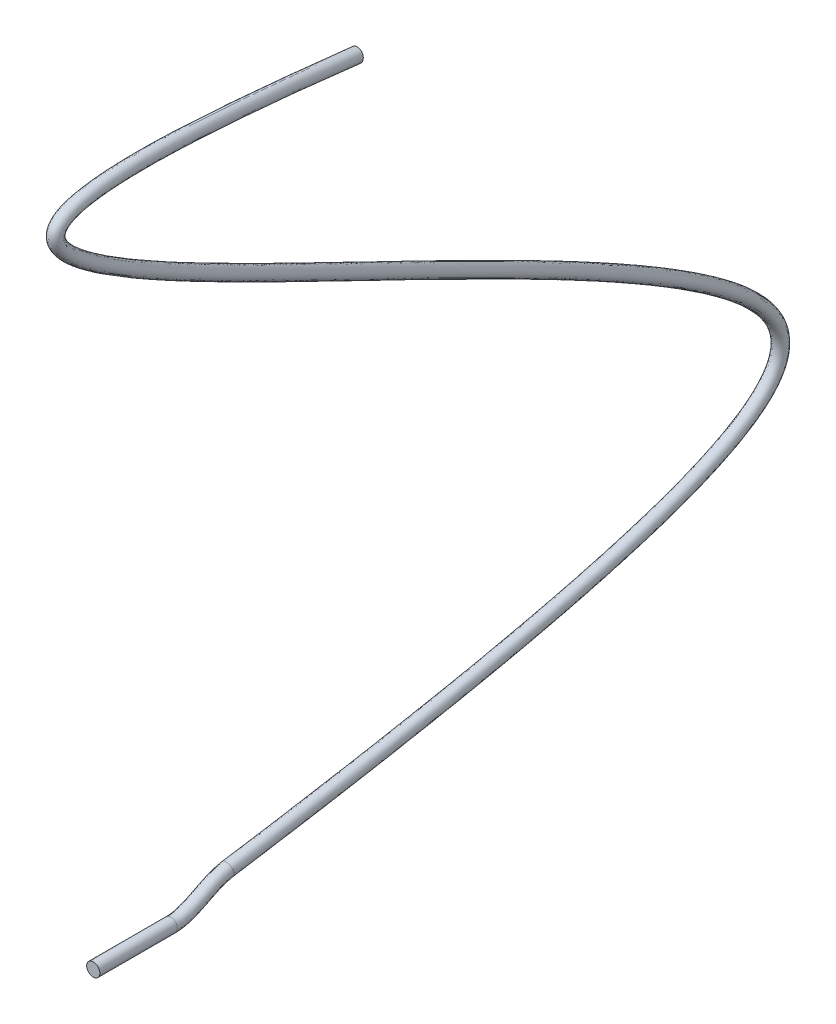
SolidWorks part; units mm, degrees
ref_plane "Front Plane" through (0, 0, 0) normal (0, 0, 1) x (1, 0, 0)
ref_plane "Top Plane" through (0, 0, 0) normal (0, 1, 0) x (1, 0, 0)
ref_plane "Right Plane" through (0, 0, 0) normal (1, 0, 0) x (0, 0, -1)
sketch "Sketch1" plane through (0, 0, 0) normal (1, 0, 0) x (0, 0, -1)
  line L0 (0, 0) -> (656.7697, 0) construction
  line L1 (0, 0) -> (35.2012, 0)
  spline S0 degree 3 poles (60.9929, 9.0183) (331.9133, 51.5032) (369.9706, 141.3951) (-216.4397, 339.8282) (119.6545, 300) knots 0.024788 0.024788 0.024788 0.024788 0.377483 1 1 1 1
  spline S1 degree 3 poles (35.2012, 0) (44.6011, 0) (51.9952, 7.6074) (60.9929, 9.0183) knots 0 0 0 0 1 1 1 1
  dimension "D2" = 300
sketch "Sketch2" plane through (0, 0, 0) normal (0, 0, 1) x (1, 0, 0)
  circle A0 centre (0, 0) radius 3
sketch "Sketch3" plane through (0, 0, 0) normal (0, 0, 1) x (1, 0, 0)
  circle A0 centre (0, 0) radius 3
sweep "Sweep2" add profiles "Sketch2" path "Sketch1"
sketch "Sketch4" plane through (0, 0, 0) normal (1, 0, 0) x (0, 0, -1)
